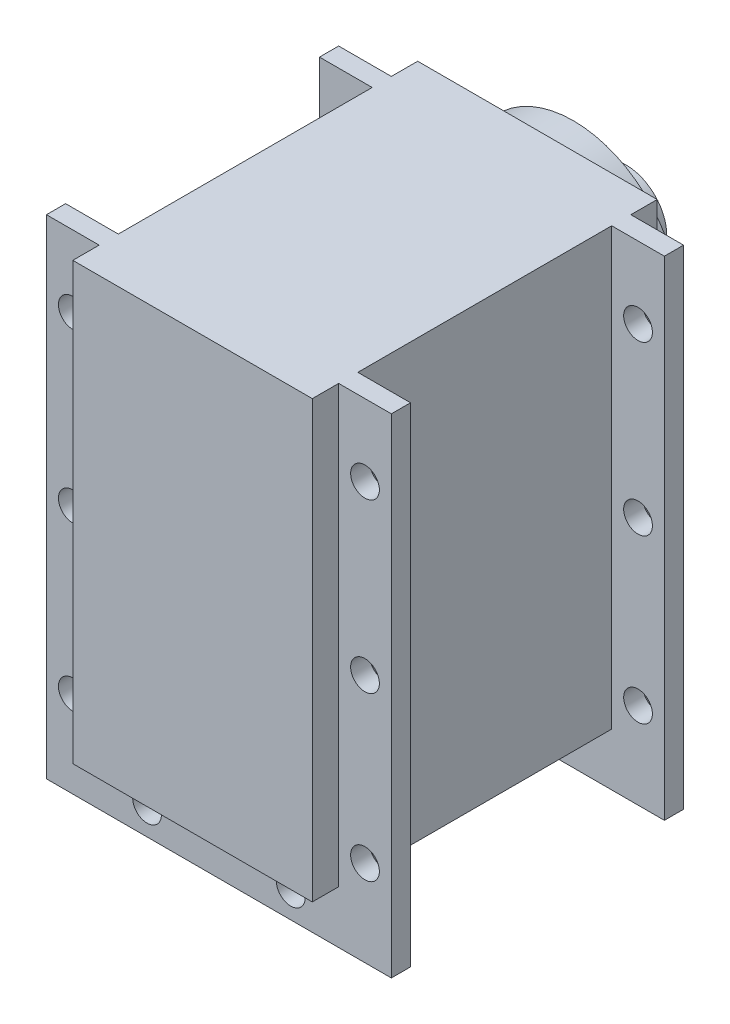
SolidWorks part; units mm, degrees
ref_plane "Front Plane" through (0, 0, 0) normal (0, 0, 1) x (1, 0, 0)
ref_plane "Top Plane" through (0, 0, 0) normal (0, 1, 0) x (1, 0, 0)
ref_plane "Right Plane" through (0, 0, 0) normal (1, 0, 0) x (0, 0, -1)
sketch "Sketch1" plane through (0, 0, 0) normal (0, 0, 1) x (1, 0, 0)
  line L1 (-12.5, -22.75) -> (12.5, -22.75)
  line L2 (-12.5, -22.75) -> (-12.5, 22.75)
  line L3 (-12.5, 22.75) -> (12.5, 22.75)
  line L4 (12.5, -22.75) -> (12.5, 22.75)
  line L5 (-12.5, -22.75) -> (12.5, 22.75) construction
  line L6 (-12.5, 22.75) -> (12.5, -22.75) construction
  point P0 (0, 0)
  dimension "D1" = 25
  dimension "D2" = 45.5
extrude "Boss-Extrude1" add sketch "Sketch1" along normal blind 36
sketch "Sketch2" plane through (0, 0, 0) normal (0, 0, -1) x (-1, 0, 0)
  line L0 (-12.5, 22.75) -> (12.5, 22.75) construction
  line L1 (-18, 22.75) -> (18, 22.75)
  line L2 (-18, 22.75) -> (-18, -28.25)
  line L3 (-18, -28.25) -> (18, -28.25)
  line L4 (18, 22.75) -> (18, -28.25)
  line L5 (-12.5, -22.75) -> (-12.5, 22.75) construction
  line L6 (12.5, 22.75) -> (12.5, -22.75) construction
  line L7 (12.5, -22.75) -> (-12.5, -22.75) construction
  line L8 (-18, 20.9329) -> (-12.5, 20.9329) construction
  line L9 (12.5, 18.8932) -> (18, 18.8932) construction
  line L10 (2.0803, -28.25) -> (2.0803, -22.75) construction
  circle A0 centre (-15.25, 15.25) radius 1.5
  circle A1 centre (-15.25, -2.25) radius 1.5
  circle A2 centre (-15.25, -19.25) radius 1.5
  circle A3 centre (-7.5, -25.5) radius 1.5
  circle A4 centre (7.5, -25.5) radius 1.5
  circle A5 centre (15.25, -19.25) radius 1.5
  circle A6 centre (15.25, -2.25) radius 1.5
  circle A7 centre (15.25, 15.25) radius 1.5
  point P28 (2.0803, -25.5)
  point P29 (-15.25, 20.9329)
  point P32 (15.25, 18.8932)
  dimension "D4" = 3
  dimension "D5" = 7.5
  dimension "D1" = 5.5
  dimension "D2" = 5.5
  dimension "D3" = 5.5
  dimension "D6" = 25
  dimension "D7" = 42
  dimension "D8" = 5
  dimension "D9" = 5
extrude "Boss-Extrude2" add sketch "Sketch2" against normal blind 2 from offset 2.75 offset against normal yes
sketch "Sketch3" plane through (0, 0, 0) normal (0, 0, -1) x (-1, 0, 0)
  line L0 (-12.5, 22.75) -> (12.5, 22.75) construction
  circle A0 centre (0, 10.75) radius 11
  point P5 (0, 22.75)
  dimension "D1" = 22
  dimension "D2" = 12
extrude "Boss-Extrude3" add sketch "Sketch3" along normal blind 3.75
sketch "Sketch4" plane through (0, 0, -3.75) normal (0, 0, -1) x (-1, 0, 0)
  circle A0 centre (0, 18.75) radius 1.5
  circle A1 centre (0, 10.75) radius 11 construction
  circle A2 centre (-5.6569, 16.4069) radius 1.5
  circle A3 centre (-8, 10.75) radius 1.5
  circle A4 centre (-5.6569, 5.0931) radius 1.5
  circle A5 centre (0, 2.75) radius 1.5
  circle A6 centre (5.6569, 5.0931) radius 1.5
  circle A7 centre (8, 10.75) radius 1.5
  circle A8 centre (5.6569, 16.4069) radius 1.5
  point P21 (0, 10.75)
  dimension "D1" = 3
  dimension "D2" = 8
  dimension "D3" = 8
extrude "Cut-Extrude1" cut sketch "Sketch4" against normal blind 3.75
sketch "Sketch5" plane through (0, 0, -3.75) normal (0, 0, -1) x (-1, 0, 0)
  circle A0 centre (0, 10.75) radius 4.25
  dimension "D1" = 8.5
extrude "Boss-Extrude4" add sketch "Sketch5" along normal blind 5.5
sketch "Sketch6" plane through (0, 0, 36) normal (0, 0, 1) x (1, 0, 0)
  line L1 (-18, 22.75) -> (18, 22.75)
  line L2 (-18, 22.75) -> (-18, -28.25)
  line L3 (-18, -28.25) -> (18, -28.25)
  line L4 (18, 22.75) -> (18, -28.25)
  line L8 (-18, 20.9329) -> (-12.5, 20.9329) construction
  line L9 (12.5, 18.8932) -> (18, 18.8932) construction
  line L10 (2.0803, -28.25) -> (2.0803, -22.75) construction
  circle A0 centre (-15.25, 15.25) radius 1.5
  circle A1 centre (-15.25, -2.25) radius 1.5
  circle A2 centre (-15.25, -19.25) radius 1.5
  circle A3 centre (-7.5, -25.5) radius 1.5
  circle A4 centre (7.5, -25.5) radius 1.5
  circle A5 centre (15.25, -19.25) radius 1.5
  circle A6 centre (15.25, -2.25) radius 1.5
  circle A7 centre (15.25, 15.25) radius 1.5
  point P28 (2.0803, -25.5)
  point P29 (-15.25, 20.9329)
  point P32 (15.25, 18.8932)
  dimension "D4" = 3
  dimension "D5" = 7.5
  dimension "D1" = 36
  dimension "D6" = 25
  dimension "D7" = 42
extrude "Boss-Extrude5" add sketch "Sketch6" against normal blind 2 from offset 2.75 offset against normal yes
